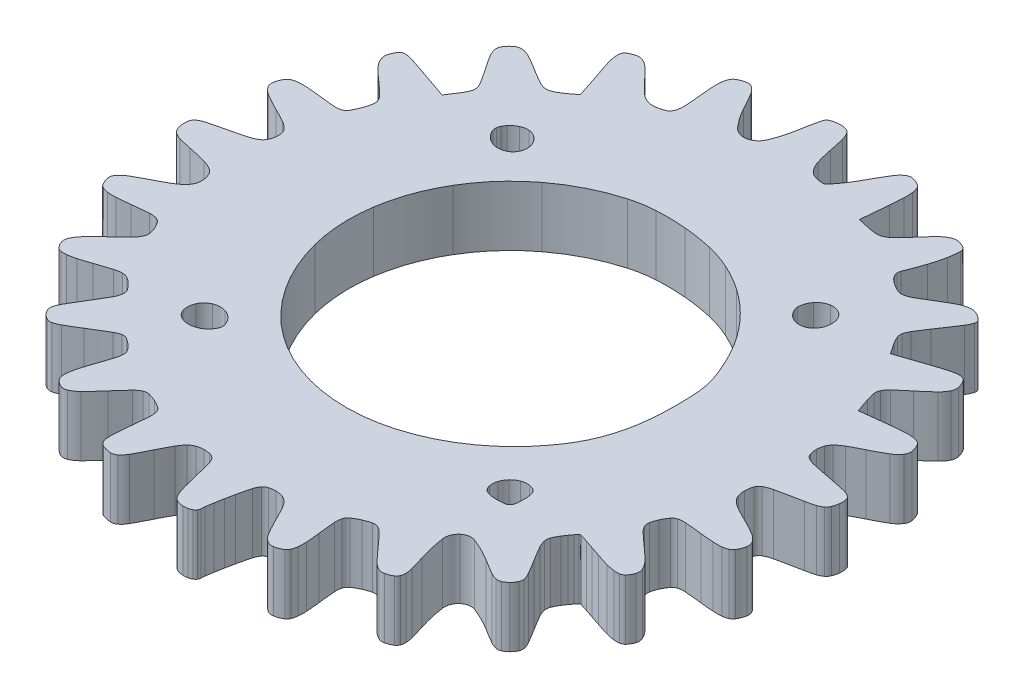
SolidWorks part; units mm, degrees
ref_plane "Front Plane" through (0, 0, 0) normal (0, 0, 1) x (1, 0, 0)
ref_plane "Top Plane" through (0, 0, 0) normal (0, 1, 0) x (1, 0, 0)
ref_plane "Right Plane" through (0, 0, 0) normal (1, 0, 0) x (0, 0, -1)
sketch "Sketch1" plane through (0, 0, 0) normal (0, 1, 0) x (1, 0, 0)
  line L117 (11035.1777, 9201.8668) -> (11035.0579, 9201.6839)
  line L118 (11035.0579, 9201.6839) -> (11034.6261, 9201.8325)
  line L119 (11043.5335, 9200.6497) -> (11043.0767, 9200.5967)
  line L120 (11043.0767, 9200.5967) -> (11042.9953, 9200.8302)
  line L121 (11042.9884, 9201.8431) -> (11042.5214, 9201.6854)
  line L122 (11042.5214, 9201.6854) -> (11042.4021, 9201.8675)
  line L123 (11040.5559, 9203.3117) -> (11040.3294, 9203.3614)
  line L124 (11040.3294, 9203.3614) -> (11040.3711, 9203.8218)
  arc A653 (11038.6129, 9204.5147) -> (11038.597, 9204.4764) centre (11038.7402, 9204.4394) ccw
  arc A654 (11038.597, 9204.4764) -> (11038.5732, 9204.3788) centre (11042.1329, 9203.5631) ccw
  arc A655 (11038.5732, 9204.3788) -> (11038.5484, 9204.261) centre (11041.9829, 9203.5975) ccw
  arc A656 (11038.5484, 9204.261) -> (11038.5253, 9204.1322) centre (11043.3345, 9203.3363) ccw
  arc A657 (11038.4093, 9203.7376) -> (11038.5253, 9204.1322) centre (11036.8563, 9204.4084) ccw
  arc A658 (11038.2209, 9203.5891) -> (11038.4093, 9203.7376) centre (11038.1778, 9203.8376) ccw
  arc A659 (11037.9966, 9203.6668) -> (11038.2209, 9203.5891) centre (11038.179, 9203.8308) ccw
  arc A660 (11037.7648, 9204.0003) -> (11037.9966, 9203.6668) centre (11039.2056, 9204.7541) ccw
  arc A661 (11037.7648, 9204.0003) -> (11037.6141, 9204.268) centre (11033.3581, 9201.6948) ccw
  arc A662 (11037.6141, 9204.268) -> (11037.5104, 9204.3797) centre (11037.2932, 9204.074) ccw
  arc A663 (11037.5104, 9204.3797) -> (11037.406, 9204.4022) centre (11037.432, 9204.2694) ccw
  arc A664 (11037.406, 9204.4022) -> (11037.2736, 9204.3494) centre (11037.4802, 9204.0231) ccw
  arc A665 (11037.2736, 9204.3494) -> (11037.2246, 9204.2922) centre (11037.3419, 9204.2415) ccw
  arc A666 (11037.2246, 9204.2922) -> (11037.1997, 9204.1986) centre (11037.526, 9204.1619) ccw
  arc A667 (11037.1997, 9204.1986) -> (11037.1958, 9204.0539) centre (11038.0452, 9204.1034) ccw
  arc A668 (11037.1958, 9204.0539) -> (11037.2145, 9203.8246) centre (11042.2008, 9204.3458) ccw
  arc A669 (11037.2351, 9203.5815) -> (11037.2145, 9203.8246) centre (11031.0398, 9203.1792) ccw
  arc A670 (11037.23, 9203.4472) -> (11037.2351, 9203.5815) centre (11036.5793, 9203.5389) ccw
  arc A671 (11037.2007, 9203.3683) -> (11037.23, 9203.4472) centre (11037.0356, 9203.4746) ccw
  arc A672 (11037.1437, 9203.322) -> (11037.2007, 9203.3683) centre (11037.1013, 9203.4323) ccw
  arc A673 (11036.9852, 9203.285) -> (11037.1437, 9203.322) centre (11036.9302, 9203.8781) ccw
  arc A674 (11036.8544, 9203.3053) -> (11036.9852, 9203.285) centre (11036.9602, 9203.5545) ccw
  arc A675 (11036.7186, 9203.3933) -> (11036.8544, 9203.3053) centre (11037.0379, 9203.7374) ccw
  arc A676 (11036.5332, 9203.5812) -> (11036.7186, 9203.3933) centre (11038.7613, 9205.5943) ccw
  arc A677 (11036.5332, 9203.5812) -> (11036.3454, 9203.7751) centre (11033.6494, 9200.9759) ccw
  arc A678 (11036.3454, 9203.7751) -> (11036.2207, 9203.859) centre (11036.045, 9203.4633) ccw
  arc A679 (11036.2207, 9203.859) -> (11036.1111, 9203.8714) centre (11036.1462, 9203.6912) ccw
  arc A680 (11036.1111, 9203.8714) -> (11035.989, 9203.8228) centre (11036.1789, 9203.5238) ccw
  arc A681 (11035.989, 9203.8228) -> (11035.9503, 9203.7692) centre (11036.037, 9203.7473) ccw
  arc A682 (11035.9503, 9203.7692) -> (11035.9444, 9203.6827) centre (11036.1848, 9203.7098) ccw
  arc A683 (11035.9444, 9203.6827) -> (11035.9725, 9203.5455) centre (11036.7209, 9203.7703) ccw
  arc A684 (11035.9725, 9203.5455) -> (11036.0462, 9203.3167) centre (11041.7937, 9205.2942) ccw
  arc A685 (11036.1049, 9203.1443) -> (11036.0462, 9203.3167) centre (11008.7323, 9193.9194) ccw
  arc A686 (11036.1543, 9202.9952) -> (11036.1049, 9203.1443) centre (11020.8775, 9198.0125) ccw
  arc A687 (11036.1965, 9202.8654) -> (11036.1543, 9202.9952) centre (10991.7342, 9188.507) ccw
  arc A688 (11036.1993, 9202.8472) -> (11036.1965, 9202.8654) centre (11036.14, 9202.8472) ccw
  arc A689 (11036.1928, 9202.8332) -> (11036.1993, 9202.8472) centre (11036.1811, 9202.8472) ccw
  arc A690 (11036.1461, 9202.7951) -> (11036.1928, 9202.8332) centre (11034.9769, 9204.2751) ccw
  arc A691 (11036.0876, 9202.7513) -> (11036.1461, 9202.7951) centre (11035.2969, 9203.8701) ccw
  arc A692 (11036.0182, 9202.7041) -> (11036.0876, 9202.7513) centre (11034.7113, 9204.6986) ccw
  arc A693 (11035.9009, 9202.6449) -> (11036.0182, 9202.7041) centre (11035.6991, 9203.191) ccw
  arc A694 (11035.8065, 9202.6382) -> (11035.9009, 9202.6449) centre (11035.8422, 9202.8038) ccw
  arc A695 (11035.6891, 9202.6833) -> (11035.8065, 9202.6382) centre (11035.8932, 9203.0398) ccw
  arc A696 (11035.4481, 9202.8271) -> (11035.6891, 9202.6833) centre (11039.5312, 9209.3954) ccw
  arc A697 (11035.4481, 9202.8271) -> (11035.2361, 9202.9524) centre (11032.5234, 9198.1222) ccw
  arc A698 (11035.2361, 9202.9524) -> (11035.111, 9203.0048) centre (11034.9474, 9202.4383) ccw
  arc A699 (11035.111, 9203.0048) -> (11035.0216, 9203.0093) centre (11035.0567, 9202.8169) ccw
  arc A700 (11035.0216, 9203.0093) -> (11034.9435, 9202.9728) centre (11035.0522, 9202.8418) ccw
  arc A701 (11034.9435, 9202.9728) -> (11034.8588, 9202.8741) centre (11035.1898, 9202.676) ccw
  arc A702 (11034.8588, 9202.8741) -> (11034.8424, 9202.7778) centre (11034.9745, 9202.8049) ccw
  arc A703 (11034.8424, 9202.7778) -> (11034.8945, 9202.6473) centre (11035.2309, 9202.8574) ccw
  arc A704 (11034.8945, 9202.6473) -> (11035.0626, 9202.391) centre (11040.7395, 9206.2969) ccw
  arc A705 (11035.2027, 9202.1782) -> (11035.0626, 9202.391) centre (11029.9216, 9198.8539) ccw
  arc A706 (11035.246, 9202.0727) -> (11035.2027, 9202.1782) centre (11034.9222, 9202.0016) ccw
  arc A707 (11035.2387, 9201.9839) -> (11035.246, 9202.0727) centre (11035.0979, 9202.0402) ccw
  arc A708 (11035.1777, 9201.8668) -> (11035.2387, 9201.9839) centre (11034.6237, 9202.2298) ccw
  arc A709 (11034.6261, 9201.8325) -> (11034.2708, 9201.9509) centre (11028.3283, 9183.5277) ccw
  arc A710 (11034.2708, 9201.9509) -> (11034.1488, 9201.9693) centre (11034.1537, 9201.5877) ccw
  arc A711 (11034.1488, 9201.9693) -> (11034.0798, 9201.9328) centre (11034.1499, 9201.8837) ccw
  arc A712 (11034.0798, 9201.9328) -> (11034.0264, 9201.8248) centre (11034.4064, 9201.7042) ccw
  arc A713 (11034.0264, 9201.8248) -> (11034.021, 9201.7326) centre (11034.2051, 9201.7681) ccw
  arc A714 (11034.021, 9201.7326) -> (11034.0587, 9201.6382) centre (11034.2861, 9201.7837) ccw
  arc A715 (11034.0587, 9201.6382) -> (11034.15, 9201.5252) centre (11034.6144, 9201.9938) ccw
  arc A716 (11034.15, 9201.5252) -> (11034.3193, 9201.3671) centre (11036.9105, 9204.3109) ccw
  arc A717 (11034.5286, 9201.1752) -> (11034.3193, 9201.3671) centre (11029.6558, 9196.0692) ccw
  arc A718 (11034.6009, 9201.0753) -> (11034.5286, 9201.1752) centre (11034.294, 9200.9293) ccw
  arc A719 (11034.6139, 9200.9785) -> (11034.6009, 9201.0753) centre (11034.4566, 9201.0066) ccw
  arc A720 (11034.5736, 9200.8322) -> (11034.6139, 9200.9785) centre (11033.8008, 9201.124) ccw
  arc A721 (11034.5074, 9200.6901) -> (11034.5736, 9200.8322) centre (11033.5986, 9201.2003) ccw
  arc A722 (11034.4405, 9200.6346) -> (11034.5074, 9200.6901) centre (11034.4015, 9200.7495) ccw
  arc A723 (11034.332, 9200.6214) -> (11034.4405, 9200.6346) centre (11034.3545, 9200.8886) ccw
  arc A724 (11034.0378, 9200.6508) -> (11034.332, 9200.6214) centre (11035.1164, 9209.9448) ccw
  arc A725 (11034.0378, 9200.6508) -> (11033.8148, 9200.6714) centre (11033.4856, 9195.8937) ccw
  arc A726 (11033.8148, 9200.6714) -> (11033.6725, 9200.6691) centre (11033.757, 9199.8321) ccw
  arc A727 (11033.6725, 9200.6691) -> (11033.5801, 9200.6459) centre (11033.7054, 9200.3429) ccw
  arc A728 (11033.5801, 9200.6459) -> (11033.5242, 9200.599) centre (11033.6262, 9200.5343) ccw
  arc A729 (11033.5242, 9200.599) -> (11033.4711, 9200.4604) centre (11033.8417, 9200.3978) ccw
  arc A730 (11033.4711, 9200.4604) -> (11033.4967, 9200.3476) centre (11033.621, 9200.4351) ccw
  arc A731 (11033.4967, 9200.3476) -> (11033.6154, 9200.238) centre (11033.8114, 9200.5692) ccw
  arc A732 (11033.6154, 9200.238) -> (11033.8786, 9200.0958) centre (11035.5589, 9203.5218) ccw
  arc A733 (11034.1113, 9199.9745) -> (11033.8786, 9200.0958) centre (11031.5049, 9195.2558) ccw
  arc A734 (11034.2221, 9199.8913) -> (11034.1113, 9199.9745) centre (11033.871, 9199.5395) ccw
  arc A735 (11034.2708, 9199.8066) -> (11034.2221, 9199.8913) centre (11034.0899, 9199.7589) ccw
  arc A736 (11034.2787, 9199.6966) -> (11034.2708, 9199.8066) centre (11033.9842, 9199.7309) ccw
  arc A737 (11034.2454, 9199.5896) -> (11034.2787, 9199.6966) centre (11033.9767, 9199.7318) ccw
  arc A738 (11034.1781, 9199.5187) -> (11034.2454, 9199.5896) centre (11034.0845, 9199.6748) ccw
  arc A739 (11034.0484, 9199.4633) -> (11034.1781, 9199.5187) centre (11033.9124, 9199.9616) ccw
  arc A740 (11033.7763, 9199.3951) -> (11034.0484, 9199.4633) centre (11032.3048, 9205.8509) ccw
  arc A741 (11033.7763, 9199.3951) -> (11033.4863, 9199.324) centre (11035.7781, 9190.6128) ccw
  arc A742 (11033.4863, 9199.324) -> (11033.3725, 9199.2729) centre (11033.5833, 9198.9554) ccw
  arc A743 (11033.3725, 9199.2729) -> (11033.325, 9199.204) centre (11033.4347, 9199.1793) ccw
  arc A744 (11033.325, 9199.204) -> (11033.3191, 9199.0916) centre (11033.6508, 9199.1305) ccw
  arc A745 (11033.3191, 9199.0916) -> (11033.3483, 9198.9861) centre (11033.674, 9199.1332) ccw
  arc A746 (11033.3483, 9198.9861) -> (11033.4057, 9198.9182) centre (11033.4963, 9199.0529) ccw
  arc A747 (11033.4057, 9198.9182) -> (11033.5126, 9198.8695) centre (11033.6054, 9199.2151) ccw
  arc A748 (11033.5126, 9198.8695) -> (11033.7228, 9198.82) centre (11034.4185, 9202.2426) ccw
  arc A749 (11034.0329, 9198.7472) -> (11033.7228, 9198.82) centre (11032.6663, 9193.6222) ccw
  arc A750 (11034.1894, 9198.6765) -> (11034.0329, 9198.7472) centre (11033.8972, 9198.2382) ccw
  arc A751 (11034.2669, 9198.5811) -> (11034.1894, 9198.6765) centre (11034.0742, 9198.5038) ccw
  arc A752 (11034.2943, 9198.439) -> (11034.2669, 9198.5811) centre (11033.9128, 9198.439) ccw
  arc A753 (11034.272, 9198.3394) -> (11034.2943, 9198.439) centre (11034.0608, 9198.439) ccw
  arc A754 (11034.2085, 9198.2523) -> (11034.272, 9198.3394) centre (11034.0122, 9198.462) ccw
  arc A755 (11034.0876, 9198.1622) -> (11034.2085, 9198.2523) centre (11033.7485, 9198.7436) ccw
  arc A756 (11033.8752, 9198.0466) -> (11034.0876, 9198.1622) centre (11032.0317, 9201.6875) ccw
  arc A757 (11033.8752, 9198.0466) -> (11033.6066, 9197.9005) centre (11036.2092, 9193.4371) ccw
  arc A758 (11033.6066, 9197.9005) -> (11033.496, 9197.8009) centre (11033.7907, 9197.5848) ccw
  arc A759 (11033.496, 9197.8009) -> (11033.4736, 9197.6998) centre (11033.5997, 9197.7249) ccw
  arc A760 (11033.4736, 9197.6998) -> (11033.5256, 9197.5698) centre (11033.8488, 9197.7744) ccw
  arc A761 (11033.5256, 9197.5698) -> (11033.5823, 9197.5214) centre (11033.6321, 9197.6372) ccw
  arc A762 (11033.5823, 9197.5214) -> (11033.6746, 9197.4972) centre (11033.7081, 9197.8141) ccw
  arc A763 (11033.6746, 9197.4972) -> (11033.8176, 9197.4945) centre (11033.7621, 9198.3244) ccw
  arc A764 (11033.8176, 9197.4945) -> (11034.0445, 9197.5149) centre (11033.4865, 9202.4473) ccw
  arc A765 (11034.3267, 9197.542) -> (11034.0445, 9197.5149) centre (11034.985, 9189.2027) ccw
  arc A766 (11034.4448, 9197.5315) -> (11034.3267, 9197.542) centre (11034.3547, 9197.1879) ccw
  arc A767 (11034.518, 9197.483) -> (11034.4448, 9197.5315) centre (11034.4102, 9197.3996) ccw
  arc A768 (11034.5842, 9197.3733) -> (11034.518, 9197.483) centre (11034.0774, 9197.1423) ccw
  arc A769 (11034.6199, 9197.2539) -> (11034.5842, 9197.3733) centre (11034.1698, 9197.1845) ccw
  arc A770 (11034.6054, 9197.1616) -> (11034.6199, 9197.2539) centre (11034.4678, 9197.2304) ccw
  arc A771 (11034.5308, 9197.058) -> (11034.6054, 9197.1616) centre (11034.2492, 9197.3396) ccw
  arc A772 (11034.3308, 9196.866) -> (11034.5308, 9197.058) centre (11029.7063, 9201.8829) ccw
  arc A773 (11034.3308, 9196.866) -> (11034.1092, 9196.6484) centre (11037.6511, 9193.2639) ccw
  arc A774 (11034.1092, 9196.6484) -> (11034.016, 9196.5092) centre (11034.4626, 9196.3107) ccw
  arc A775 (11034.016, 9196.5092) -> (11034.0088, 9196.3977) centre (11034.1633, 9196.4437) ccw
  arc A776 (11034.0088, 9196.3977) -> (11034.074, 9196.2882) centre (11034.2577, 9196.4719) ccw
  arc A777 (11034.074, 9196.2882) -> (11034.1372, 9196.2567) centre (11034.1529, 9196.3671) ccw
  arc A778 (11034.1372, 9196.2567) -> (11034.235, 9196.2557) centre (11034.19, 9196.6288) ccw
  arc A779 (11034.235, 9196.2557) -> (11034.376, 9196.2843) centre (11034.1279, 9197.1435) ccw
  arc A780 (11034.376, 9196.2843) -> (11034.5821, 9196.3495) centre (11033.1838, 9200.4136) ccw
  arc A781 (11034.8406, 9196.4338) -> (11034.5821, 9196.3495) centre (11037.3033, 9188.4399) ccw
  arc A782 (11034.963, 9196.4543) -> (11034.8406, 9196.4338) centre (11034.9791, 9195.9842) ccw
  arc A783 (11035.0508, 9196.4345) -> (11034.963, 9196.4543) centre (11034.9691, 9196.2771) ccw
  arc A784 (11035.1453, 9196.3688) -> (11035.0508, 9196.4345) centre (11034.8433, 9196.0352) ccw
  arc A785 (11035.247, 9196.253) -> (11035.1453, 9196.3688) centre (11034.6935, 9195.8696) ccw
  arc A786 (11035.2692, 9196.1563) -> (11035.247, 9196.253) centre (11035.137, 9196.1768) ccw
  arc A787 (11035.2243, 9196.0279) -> (11035.2692, 9196.1563) centre (11034.9002, 9196.2134) ccw
  arc A788 (11035.0461, 9195.7277) -> (11035.2243, 9196.0279) centre (11025.6493, 9201.5096) ccw
  arc A789 (11035.0461, 9195.7277) -> (11034.9077, 9195.494) centre (11041.8735, 9191.5268) ccw
  arc A790 (11034.9077, 9195.494) -> (11034.8637, 9195.3813) centre (11035.2695, 9195.2879) ccw
  arc A791 (11034.8637, 9195.3813) -> (11034.8717, 9195.3005) centre (11034.9876, 9195.3528) ccw
  arc A792 (11034.8717, 9195.3005) -> (11034.9287, 9195.218) centre (11035.126, 9195.4153) ccw
  arc A793 (11034.9287, 9195.218) -> (11035.0113, 9195.1611) centre (11035.1243, 9195.4136) ccw
  arc A794 (11035.0113, 9195.1611) -> (11035.0922, 9195.1534) centre (11035.0631, 9195.2769) ccw
  arc A795 (11035.0922, 9195.1534) -> (11035.205, 9195.1981) centre (11034.9961, 9195.5609) ccw
  arc A796 (11035.205, 9195.1981) -> (11035.4394, 9195.3384) centre (11031.1618, 9202.2196) ccw
  arc A797 (11035.7404, 9195.5211) -> (11035.4394, 9195.3384) centre (11044.2561, 9181.1551) ccw
  arc A798 (11035.8508, 9195.5633) -> (11035.7404, 9195.5211) centre (11035.9185, 9195.2206) ccw
  arc A799 (11035.9365, 9195.5479) -> (11035.8508, 9195.5633) centre (11035.8739, 9195.4464) ccw
  arc A800 (11036.0538, 9195.4598) -> (11035.9365, 9195.5479) centre (11035.515, 9194.8644) ccw
  arc A801 (11036.1246, 9195.3758) -> (11036.0538, 9195.4598) centre (11035.7791, 9195.1563) ccw
  arc A802 (11036.1468, 9195.2957) -> (11036.1246, 9195.3758) centre (11036.0039, 9195.2991) ccw
  arc A803 (11036.1277, 9195.1797) -> (11036.1468, 9195.2957) centre (11035.7243, 9195.3057) ccw
  arc A804 (11036.0409, 9194.9149) -> (11036.1277, 9195.1797) centre (11026.8462, 9198.0784) ccw
  arc A805 (11036.0409, 9194.9149) -> (11035.9741, 9194.7036) centre (11040.2145, 9193.479) ccw
  arc A806 (11035.9741, 9194.7036) -> (11035.9454, 9194.5608) centre (11036.8147, 9194.4608) ccw
  arc A807 (11035.9454, 9194.5608) -> (11035.9476, 9194.46) centre (11036.3162, 9194.5182) ccw
  arc A808 (11035.9476, 9194.46) -> (11035.9802, 9194.3877) centre (11036.0954, 9194.4833) ccw
  arc A809 (11035.9802, 9194.3877) -> (11036.0857, 9194.309) centre (11036.196, 9194.5667) ccw
  arc A810 (11036.0857, 9194.309) -> (11036.1929, 9194.3095) centre (11036.1388, 9194.4331) ccw
  arc A811 (11036.1929, 9194.3095) -> (11036.3273, 9194.4018) centre (11036.0193, 9194.706) ccw
  arc A812 (11036.3273, 9194.4018) -> (11036.5426, 9194.634) centre (11032.7198, 9197.9641) ccw
  arc A813 (11036.7387, 9194.851) -> (11036.5426, 9194.634) centre (11042.6359, 9189.3262) ccw
  arc A814 (11036.8358, 9194.9222) -> (11036.7387, 9194.851) centre (11036.9772, 9194.6276) ccw
  arc A815 (11036.9279, 9194.9322) -> (11036.8358, 9194.9222) centre (11036.896, 9194.7967) ccw
  arc A816 (11037.0659, 9194.885) -> (11036.9279, 9194.9322) centre (11036.7574, 9194.208) ccw
  arc A817 (11037.1951, 9194.8114) -> (11037.0659, 9194.885) centre (11036.7237, 9194.1342) ccw
  arc A818 (11037.2489, 9194.737) -> (11037.1951, 9194.8114) centre (11037.1156, 9194.6973) ccw
  arc A819 (11037.2619, 9194.6186) -> (11037.2489, 9194.737) centre (11036.9304, 9194.6421) ccw
  arc A820 (11037.2357, 9194.3153) -> (11037.2619, 9194.6186) centre (11027.5857, 9195.304) ccw
  arc A821 (11037.2357, 9194.3153) -> (11037.2144, 9194.0614) centre (11044.0786, 9193.6142) ccw
  arc A822 (11037.2144, 9194.0614) -> (11037.2196, 9193.925) centre (11037.8755, 9194.0183) ccw
  arc A823 (11037.2196, 9193.925) -> (11037.25, 9193.8455) centre (11037.4093, 9193.952) ccw
  arc A824 (11037.25, 9193.8455) -> (11037.3092, 9193.7982) centre (11037.3541, 9193.9151) ccw
  arc A825 (11037.3092, 9193.7982) -> (11037.4516, 9193.765) centre (11037.4998, 9194.2949) ccw
  arc A826 (11037.4516, 9193.765) -> (11037.5481, 9193.7939) centre (11037.4639, 9193.8999) ccw
  arc A827 (11037.5481, 9193.7939) -> (11037.6368, 9193.8989) centre (11037.331, 9194.0673) ccw
  arc A828 (11037.6368, 9193.8989) -> (11037.7781, 9194.1705) centre (11031.9657, 9197.0212) ccw
  arc A829 (11037.8967, 9194.3965) -> (11037.7781, 9194.1705) centre (11041.9659, 9192.1167) ccw
  arc A830 (11037.9835, 9194.5124) -> (11037.8967, 9194.3965) centre (11038.377, 9194.1274) ccw
  arc A831 (11038.0729, 9194.5697) -> (11037.9835, 9194.5124) centre (11038.1524, 9194.3471) ccw
  arc A832 (11038.1881, 9194.5896) -> (11038.0729, 9194.5697) centre (11038.1881, 9194.2471) ccw
  arc A833 (11038.2919, 9194.5792) -> (11038.1881, 9194.5896) centre (11038.1881, 9194.07) ccw
  arc A834 (11038.3608, 9194.5464) -> (11038.2919, 9194.5792) centre (11038.2603, 9194.424) ccw
  arc A835 (11038.408, 9194.4841) -> (11038.3608, 9194.5464) centre (11038.2539, 9194.4162) ccw
  arc A836 (11038.4432, 9194.3801) -> (11038.408, 9194.4841) centre (11037.8431, 9194.2352) ccw
  arc A837 (11038.4432, 9194.3801) -> (11038.5666, 9193.8866) centre (11068.7521, 9201.6963) ccw
  arc A838 (11038.5666, 9193.8866) -> (11038.6332, 9193.7079) centre (11039.4563, 9194.1168) ccw
  arc A839 (11038.6332, 9193.7079) -> (11038.7114, 9193.6283) centre (11038.7944, 9193.788) ccw
  arc A840 (11038.7114, 9193.6283) -> (11038.8312, 9193.599) centre (11038.8312, 9193.8587) ccw
  arc A841 (11038.8312, 9193.599) -> (11038.9077, 9193.6066) centre (11038.8312, 9193.992) ccw
  arc A842 (11038.9077, 9193.6066) -> (11038.9674, 9193.6293) centre (11038.8706, 9193.7936) ccw
  arc A843 (11038.9674, 9193.6293) -> (11039.0051, 9193.6648) centre (11038.9079, 9193.7303) ccw
  arc A844 (11039.0051, 9193.6648) -> (11039.0187, 9193.7096) centre (11038.9386, 9193.7096) ccw
  arc A845 (11039.0234, 9193.7742) -> (11039.0187, 9193.7096) centre (11039.4732, 9193.7096) ccw
  arc A846 (11039.043, 9193.9007) -> (11039.0234, 9193.7742) centre (11044.6941, 9192.9593) ccw
  arc A847 (11039.0697, 9194.0495) -> (11039.043, 9193.9007) centre (11045.0684, 9192.8969) ccw
  arc A848 (11039.1012, 9194.2049) -> (11039.0697, 9194.0495) centre (11046.3352, 9192.6535) ccw
  arc A849 (11039.1554, 9194.4283) -> (11039.1012, 9194.2049) centre (11043.3501, 9193.2937) ccw
  arc A850 (11039.2038, 9194.5275) -> (11039.1554, 9194.4283) centre (11039.4374, 9194.3521) ccw
  arc A851 (11039.2733, 9194.5744) -> (11039.2038, 9194.5275) centre (11039.3063, 9194.4505) ccw
  arc A852 (11039.3902, 9194.5896) -> (11039.2733, 9194.5744) centre (11039.3902, 9194.1351) ccw
  arc A853 (11039.5067, 9194.5699) -> (11039.3902, 9194.5896) centre (11039.3902, 9194.2367) ccw
  arc A854 (11039.5964, 9194.5129) -> (11039.5067, 9194.5699) centre (11039.4294, 9194.3487) ccw
  arc A855 (11039.6831, 9194.3974) -> (11039.5964, 9194.5129) centre (11039.2086, 9194.1317) ccw
  arc A856 (11039.8021, 9194.1705) -> (11039.6831, 9194.3974) centre (11035.5761, 9192.0979) ccw
  arc A857 (11039.8021, 9194.1705) -> (11039.9433, 9193.9094) centre (11043.1629, 9195.8188) ccw
  arc A858 (11039.9433, 9193.9094) -> (11040.0526, 9193.7916) centre (11040.2711, 9194.1038) ccw
  arc A859 (11040.0526, 9193.7916) -> (11040.1652, 9193.7663) centre (11040.1396, 9193.916) ccw
  arc A860 (11040.1652, 9193.7663) -> (11040.3036, 9193.8196) centre (11040.1016, 9194.1384) ccw
  arc A861 (11040.3036, 9193.8196) -> (11040.3507, 9193.8756) centre (11040.2391, 9193.9215) ccw
  arc A862 (11040.3507, 9193.8756) -> (11040.3738, 9193.9684) centre (11040.0457, 9194.001) ccw
  arc A863 (11040.3738, 9193.9684) -> (11040.3759, 9194.1117) centre (11039.5265, 9194.0526) ccw
  arc A864 (11040.3759, 9194.1117) -> (11040.355, 9194.3369) centre (11035.4778, 9193.7709) ccw
  arc A865 (11040.3263, 9194.6268) -> (11040.355, 9194.3369) centre (11049.052, 9195.3463) ccw
  arc A866 (11040.3381, 9194.7417) -> (11040.3263, 9194.6268) centre (11040.6392, 9194.6526) ccw
  arc A867 (11040.3908, 9194.8145) -> (11040.3381, 9194.7417) centre (11040.4681, 9194.7032) ccw
  arc A868 (11040.5179, 9194.887) -> (11040.3908, 9194.8145) centre (11040.86, 9194.1392) ccw
  arc A869 (11040.6539, 9194.9332) -> (11040.5179, 9194.887) centre (11040.8114, 9194.2454) ccw
  arc A870 (11040.7463, 9194.9228) -> (11040.6539, 9194.9332) centre (11040.6853, 9194.7959) ccw
  arc A871 (11040.8446, 9194.8512) -> (11040.7463, 9194.9228) centre (11040.6008, 9194.6199) ccw
  arc A872 (11041.0422, 9194.6352) -> (11040.8446, 9194.8512) centre (11034.9927, 9189.3007) ccw
  arc A873 (11041.0422, 9194.6352) -> (11041.2542, 9194.4054) centre (11046.2114, 9199.1935) ccw
  arc A874 (11041.2542, 9194.4054) -> (11041.3742, 9194.3167) centre (11041.5796, 9194.7197) ccw
  arc A875 (11041.3742, 9194.3167) -> (11041.4768, 9194.303) centre (11041.4448, 9194.4553) ccw
  arc A876 (11041.4768, 9194.303) -> (11041.5976, 9194.352) centre (11041.4017, 9194.6611) ccw
  arc A877 (11041.5976, 9194.352) -> (11041.6426, 9194.4061) centre (11041.5363, 9194.4488) ccw
  arc A878 (11041.6426, 9194.4061) -> (11041.6552, 9194.4847) centre (11041.475, 9194.4734) ccw
  arc A879 (11041.6552, 9194.4847) -> (11041.6342, 9194.6106) centre (11041.034, 9194.4458) ccw
  arc A880 (11041.6342, 9194.6106) -> (11041.5672, 9194.8379) centre (11035.5292, 9192.9346) ccw
  arc A881 (11041.4639, 9195.2861) -> (11041.5672, 9194.8379) centre (11044.3503, 9195.7152) ccw
  arc A882 (11041.5407, 9195.4975) -> (11041.4639, 9195.2861) centre (11041.6976, 9195.3209) ccw
  arc A883 (11041.7499, 9195.5349) -> (11041.5407, 9195.4975) centre (11041.6759, 9195.3454) ccw
  arc A884 (11042.1347, 9195.3422) -> (11041.7499, 9195.5349) centre (11040.8968, 9193.3508) ccw
  arc A885 (11042.1347, 9195.3422) -> (11042.3756, 9195.1978) centre (11046.7446, 9202.7579) ccw
  arc A886 (11042.3756, 9195.1978) -> (11042.4886, 9195.1531) centre (11042.5825, 9195.5559) ccw
  arc A887 (11042.4886, 9195.1531) -> (11042.5699, 9195.1616) centre (11042.517, 9195.2747) ccw
  arc A888 (11042.5699, 9195.1616) -> (11042.6546, 9195.221) centre (11042.4431, 9195.4325) ccw
  arc A889 (11042.6546, 9195.221) -> (11042.714, 9195.3056) centre (11042.4419, 9195.4336) ccw
  arc A890 (11042.714, 9195.3056) -> (11042.7226, 9195.3867) centre (11042.6014, 9195.3586) ccw
  arc A891 (11042.7226, 9195.3867) -> (11042.6782, 9195.4993) centre (11042.3231, 9195.2941) ccw
  arc A892 (11042.6782, 9195.4993) -> (11042.5346, 9195.7389) centre (11035.1954, 9191.1766) ccw
  arc A893 (11042.3889, 9195.9828) -> (11042.5346, 9195.7389) centre (11049.2866, 9199.9362) ccw
  arc A894 (11042.3433, 9196.1012) -> (11042.3889, 9195.9828) centre (11042.7514, 9196.1906) ccw
  arc A895 (11042.3497, 9196.1961) -> (11042.3433, 9196.1012) centre (11042.5094, 9196.1376) ccw
  arc A896 (11042.4087, 9196.3135) -> (11042.3497, 9196.1961) centre (11042.8904, 9195.9979) ccw
  arc A897 (11042.456, 9196.3829) -> (11042.4087, 9196.3135) centre (11044.4033, 9195.0066) ccw
  arc A898 (11042.4997, 9196.4414) -> (11042.456, 9196.3829) centre (11043.5748, 9195.5922) ccw
  arc A899 (11042.5379, 9196.4882) -> (11042.4997, 9196.4414) centre (11043.9798, 9195.2722) ccw
  arc A900 (11042.5519, 9196.4946) -> (11042.5379, 9196.4882) centre (11042.5519, 9196.4764) ccw
  arc A901 (11042.57, 9196.4918) -> (11042.5519, 9196.4946) centre (11042.5519, 9196.4354) ccw
  arc A902 (11042.6933, 9196.4519) -> (11042.57, 9196.4918) centre (11030.2017, 9158.0477) ccw
  arc A903 (11042.8352, 9196.4049) -> (11042.6933, 9196.4519) centre (11038.184, 9182.5886) ccw
  arc A904 (11042.999, 9196.3492) -> (11042.8352, 9196.4049) centre (11034.5167, 9171.6948) ccw
  arc A905 (11042.999, 9196.3492) -> (11043.2047, 9196.2842) centre (11044.3919, 9200.3976) ccw
  arc A906 (11043.2047, 9196.2842) -> (11043.3455, 9196.2556) centre (11043.4518, 9197.1405) ccw
  arc A907 (11043.3455, 9196.2556) -> (11043.4431, 9196.2567) centre (11043.3902, 9196.6276) ccw
  arc A908 (11043.4431, 9196.2567) -> (11043.5062, 9196.2882) centre (11043.4273, 9196.3671) ccw
  arc A909 (11043.5062, 9196.2882) -> (11043.5721, 9196.3994) centre (11043.3221, 9196.4724) ccw
  arc A910 (11043.5721, 9196.3994) -> (11043.564, 9196.5126) centre (11043.4154, 9196.4451) ccw
  arc A911 (11043.564, 9196.5126) -> (11043.4683, 9196.6516) centre (11043.1272, 9196.3142) ccw
  arc A912 (11043.4683, 9196.6516) -> (11043.2459, 9196.8614) centre (11040.3186, 9193.5358) ccw
  arc A913 (11043.0397, 9197.0503) -> (11043.2459, 9196.8614) centre (11047.9403, 9202.1945) ccw
  arc A914 (11042.9661, 9197.1496) -> (11043.0397, 9197.0503) centre (11043.2888, 9197.3118) ccw
  arc A915 (11042.9531, 9197.2407) -> (11042.9661, 9197.1496) centre (11043.0949, 9197.2144) ccw
  arc A916 (11042.9925, 9197.3655) -> (11042.9531, 9197.2407) centre (11043.4816, 9197.1426) ccw
  arc A917 (11043.0607, 9197.4811) -> (11042.9925, 9197.3655) centre (11043.5732, 9197.1009) ccw
  arc A918 (11043.1338, 9197.5312) -> (11043.0607, 9197.4811) centre (11043.1698, 9197.4002) ccw
  arc A919 (11043.2508, 9197.5423) -> (11043.1338, 9197.5312) centre (11043.224, 9197.2034) ccw
  arc A920 (11043.5357, 9197.5149) -> (11043.2508, 9197.5423) centre (11042.5801, 9189.0681) ccw
  arc A921 (11043.5357, 9197.5149) -> (11043.7627, 9197.4945) centre (11044.0938, 9202.4473) ccw
  arc A922 (11043.7627, 9197.4945) -> (11043.9056, 9197.4972) centre (11043.8182, 9198.3244) ccw
  arc A923 (11043.9056, 9197.4972) -> (11043.9979, 9197.5214) centre (11043.8721, 9197.8141) ccw
  arc A924 (11043.9979, 9197.5214) -> (11044.0547, 9197.5698) centre (11043.9481, 9197.6372) ccw
  arc A925 (11044.0547, 9197.5698) -> (11044.109, 9197.7095) centre (11043.7262, 9197.7778) ccw
  arc A926 (11044.109, 9197.7095) -> (11044.0843, 9197.8226) centre (11043.9597, 9197.7361) ccw
  arc A927 (11044.0843, 9197.8226) -> (11043.9668, 9197.9319) centre (11043.7745, 9197.6076) ccw
  arc A928 (11043.9668, 9197.9319) -> (11043.705, 9198.0734) centre (11042.0517, 9194.7024) ccw
  arc A929 (11043.476, 9198.1935) -> (11043.705, 9198.0734) centre (11045.8232, 9202.3924) ccw
  arc A930 (11043.3613, 9198.28) -> (11043.476, 9198.1935) centre (11043.7336, 9198.6544) ccw
  arc A931 (11043.3053, 9198.3705) -> (11043.3613, 9198.28) centre (11043.5232, 9198.4429) ccw
  arc A932 (11043.2859, 9198.4903) -> (11043.3053, 9198.3705) centre (11043.666, 9198.4903) ccw
  arc A933 (11043.3066, 9198.6264) -> (11043.2859, 9198.4903) centre (11043.7438, 9198.4903) ccw
  arc A934 (11043.3685, 9198.7017) -> (11043.3066, 9198.6264) centre (11043.4302, 9198.5879) ccw
  arc A935 (11043.509, 9198.7536) -> (11043.3685, 9198.7017) centre (11043.6205, 9198.2365) ccw
  arc A936 (11043.9336, 9198.8411) -> (11043.509, 9198.7536) centre (11048.4057, 9176.0538) ccw
  arc A937 (11043.9336, 9198.8411) -> (11044.0952, 9198.8808) centre (11043.5906, 9200.589) ccw
  arc A938 (11044.0952, 9198.8808) -> (11044.185, 9198.927) centre (11044.019, 9199.1389) ccw
  arc A939 (11044.185, 9198.927) -> (11044.2353, 9198.9942) centre (11044.0856, 9199.0539) ccw
  arc A940 (11044.2353, 9198.9942) -> (11044.2616, 9199.0981) centre (11043.8547, 9199.146) ccw
  arc A941 (11044.2616, 9199.0981) -> (11044.2563, 9199.2132) centre (11043.9093, 9199.1395) ccw
  arc A942 (11044.2563, 9199.2132) -> (11044.2089, 9199.2803) centre (11044.1546, 9199.1916) ccw
  arc A943 (11044.2089, 9199.2803) -> (11044.0939, 9199.3266) centre (11044.0138, 9198.9614) ccw
  arc A944 (11044.0939, 9199.3266) -> (11043.7854, 9199.3895) centre (11041.7989, 9188.8617) ccw
  arc A945 (11043.4813, 9199.452) -> (11043.7854, 9199.3895) centre (11045.5592, 9208.7901) ccw
  arc A946 (11043.3604, 9199.5001) -> (11043.4813, 9199.452) centre (11043.5702, 9199.8513) ccw
  arc A947 (11043.3048, 9199.5696) -> (11043.3604, 9199.5001) centre (11043.4256, 9199.6092) ccw
  arc A948 (11043.2859, 9199.6878) -> (11043.3048, 9199.5696) centre (11043.6655, 9199.6878) ccw
  arc A949 (11043.3059, 9199.8028) -> (11043.2859, 9199.6878) centre (11043.6266, 9199.6878) ccw
  arc A950 (11043.3633, 9199.8922) -> (11043.3059, 9199.8028) centre (11043.5287, 9199.7229) ccw
  arc A951 (11043.4793, 9199.9789) -> (11043.3633, 9199.8922) centre (11043.749, 9199.4976) ccw
  arc A952 (11043.705, 9200.0974) -> (11043.4793, 9199.9789) centre (11045.7554, 9195.9167) ccw
  arc A953 (11043.705, 9200.0974) -> (11043.9662, 9200.2386) centre (11042.0567, 9203.4582) ccw
  arc A954 (11043.9662, 9200.2386) -> (11044.084, 9200.3479) centre (11043.7718, 9200.5664) ccw
  arc A955 (11044.084, 9200.3479) -> (11044.1092, 9200.4605) centre (11043.9596, 9200.4349) ccw
  arc A956 (11044.1092, 9200.4605) -> (11044.056, 9200.599) centre (11043.7372, 9200.3969) ccw
  arc A957 (11044.056, 9200.599) -> (11043.9997, 9200.6461) centre (11043.9542, 9200.5344) ccw
  arc A958 (11043.9997, 9200.6461) -> (11043.9064, 9200.6691) centre (11043.8742, 9200.3384) ccw
  arc A959 (11043.9064, 9200.6691) -> (11043.7618, 9200.671) centre (11043.8226, 9199.8078) ccw
  arc A960 (11043.7618, 9200.671) -> (11043.5335, 9200.6497) centre (11044.1186, 9195.6083) ccw
  arc A961 (11042.9593, 9200.9751) -> (11042.9953, 9200.8302) centre (11043.7643, 9201.0983) ccw
  arc A962 (11042.9743, 9201.0701) -> (11042.9593, 9200.9751) centre (11043.1155, 9200.999) ccw
  arc A963 (11043.0474, 9201.1655) -> (11042.9743, 9201.0701) centre (11043.2629, 9200.9249) ccw
  arc A964 (11043.2523, 9201.3411) -> (11043.0474, 9201.1655) centre (11047.1561, 9196.577) ccw
  arc A965 (11043.2523, 9201.3411) -> (11043.4693, 9201.5312) centre (11040.4613, 9204.7471) ccw
  arc A966 (11043.4693, 9201.5312) -> (11043.5606, 9201.6549) centre (11043.1811, 9201.8393) ccw
  arc A967 (11043.5606, 9201.6549) -> (11043.5744, 9201.7662) centre (11043.4046, 9201.7307) ccw
  arc A968 (11043.5744, 9201.7662) -> (11043.5218, 9201.8957) centre (11043.1905, 9201.6858) ccw
  arc A969 (11043.5218, 9201.8957) -> (11043.4647, 9201.9412) centre (11043.4273, 9201.8358) ccw
  arc A970 (11043.4647, 9201.9412) -> (11043.3802, 9201.9515) centre (11043.3994, 9201.7569) ccw
  arc A971 (11043.3802, 9201.9515) -> (11043.2427, 9201.9243) centre (11043.4511, 9201.232) ccw
  arc A972 (11043.2427, 9201.9243) -> (11042.9884, 9201.8431) centre (11045.5606, 9194.2261) ccw
  arc A973 (11042.3411, 9201.9835) -> (11042.4021, 9201.8675) centre (11042.973, 9202.2416) ccw
  arc A974 (11042.3328, 9202.071) -> (11042.3411, 9201.9835) centre (11042.4819, 9202.041) ccw
  arc A975 (11042.3734, 9202.174) -> (11042.3328, 9202.071) centre (11042.6418, 9202.0088) ccw
  arc A976 (11042.5047, 9202.3773) -> (11042.3734, 9202.174) centre (11047.0808, 9199.278) ccw
  arc A977 (11042.5047, 9202.3773) -> (11042.7282, 9202.7132) centre (11021.892, 9216.3376) ccw
  arc A978 (11042.7282, 9202.7132) -> (11042.7812, 9202.8289) centre (11042.3722, 9202.946) ccw
  arc A979 (11042.7812, 9202.8289) -> (11042.7643, 9202.9023) centre (11042.7063, 9202.8503) ccw
  arc A980 (11042.7643, 9202.9023) -> (11042.6751, 9202.9723) centre (11042.5209, 9202.6842) ccw
  arc A981 (11042.6751, 9202.9723) -> (11042.5761, 9203.0038) centre (11042.5405, 9202.7208) ccw
  arc A982 (11042.5761, 9203.0038) -> (11042.4752, 9202.9965) centre (11042.544, 9202.7484) ccw
  arc A983 (11042.4752, 9202.9965) -> (11042.3452, 9202.9437) centre (11042.6386, 9202.4071) ccw
  arc A984 (11042.3452, 9202.9437) -> (11042.1376, 9202.8232) centre (11044.5923, 9198.834) ccw
  arc A985 (11041.8974, 9202.6813) -> (11042.1376, 9202.8232) centre (11038.0568, 9209.4555) ccw
  arc A986 (11041.7842, 9202.6398) -> (11041.8974, 9202.6813) centre (11041.7164, 9203.0004) ccw
  arc A987 (11041.6906, 9202.6496) -> (11041.7842, 9202.6398) centre (11041.7538, 9202.8017) ccw
  arc A988 (11041.5657, 9202.7157) -> (11041.6906, 9202.6496) centre (11041.9818, 9203.3509) ccw
  arc A989 (11041.4845, 9202.7784) -> (11041.5657, 9202.7157) centre (11041.9314, 9203.2739) ccw
  arc A990 (11041.434, 9202.8408) -> (11041.4845, 9202.7784) centre (11041.6568, 9202.9695) ccw
  arc A991 (11041.4138, 9202.9027) -> (11041.434, 9202.8408) centre (11041.5694, 9202.919) ccw
  arc A992 (11041.4224, 9202.9639) -> (11041.4138, 9202.9027) centre (11041.5412, 9202.9161) ccw
  arc A993 (11041.4224, 9202.9639) -> (11041.5408, 9203.2874) centre (11036.3948, 9204.9873) ccw
  arc A994 (11041.5408, 9203.2874) -> (11041.609, 9203.5494) centre (11039.5492, 9203.9453) ccw
  arc A995 (11041.609, 9203.5494) -> (11041.6309, 9203.7432) centre (11040.3688, 9203.7878) ccw
  arc A996 (11041.6309, 9203.7432) -> (11041.5879, 9203.8248) centre (11041.5381, 9203.7465) ccw
  arc A997 (11041.5879, 9203.8248) -> (11041.4658, 9203.8723) centre (11041.4068, 9203.5399) ccw
  arc A998 (11041.4658, 9203.8723) -> (11041.3552, 9203.8578) centre (11041.4334, 9203.6898) ccw
  arc A999 (11041.3552, 9203.8578) -> (11041.2306, 9203.7704) centre (11041.5384, 9203.4646) ccw
  arc A1000 (11041.2306, 9203.7704) -> (11041.0495, 9203.574) centre (11043.7829, 9201.2343) ccw
  arc A1001 (11040.8925, 9203.4016) -> (11041.0495, 9203.574) centre (11038.1614, 9206.0461) ccw
  arc A1002 (11040.7893, 9203.324) -> (11040.8925, 9203.4016) centre (11040.595, 9203.6897) ccw
  arc A1003 (11040.6888, 9203.2982) -> (11040.7893, 9203.324) centre (11040.6858, 9203.5189) ccw
  arc A1004 (11040.5559, 9203.3117) -> (11040.6888, 9203.2982) centre (11040.6807, 9203.88) ccw
  arc A1005 (11040.3711, 9203.8218) -> (11040.3864, 9204.0498) centre (11035.5448, 9204.2594) ccw
  arc A1006 (11040.3864, 9204.0498) -> (11040.3806, 9204.1967) centre (11039.4973, 9204.0883) ccw
  arc A1007 (11040.3806, 9204.1967) -> (11040.355, 9204.2924) centre (11040.027, 9204.1533) ccw
  arc A1008 (11040.355, 9204.2924) -> (11040.3064, 9204.3497) centre (11040.2389, 9204.2432) ccw
  arc A1009 (11040.3064, 9204.3497) -> (11040.1763, 9204.4016) centre (11040.102, 9204.027) ccw
  arc A1010 (11040.1763, 9204.4016) -> (11040.0742, 9204.3797) centre (11040.1507, 9204.2723) ccw
  arc A1011 (11040.0742, 9204.3797) -> (11039.9714, 9204.2698) centre (11040.2937, 9204.0715) ccw
  arc A1012 (11039.9714, 9204.2698) -> (11039.8162, 9204.0006) centre (11044.6128, 9201.4132) ccw
  arc A1013 (11039.7231, 9203.8401) -> (11039.8162, 9204.0006) centre (11037.1546, 9205.4363) ccw
  arc A1014 (11039.6305, 9203.7047) -> (11039.7231, 9203.8401) centre (11038.1463, 9204.82) ccw
  arc A1015 (11039.5474, 9203.6025) -> (11039.6305, 9203.7047) centre (11038.238, 9204.7511) ccw
  arc A1016 (11039.5012, 9203.5815) -> (11039.5474, 9203.6025) centre (11039.501, 9203.6432) ccw
  arc A1017 (11039.3453, 9203.61) -> (11039.5012, 9203.5815) centre (11039.4999, 9204.0151) ccw
  arc A1018 (11039.2352, 9203.6921) -> (11039.3453, 9203.61) centre (11039.435, 9203.8451) ccw
  arc A1019 (11039.1551, 9203.849) -> (11039.2352, 9203.6921) centre (11039.6237, 9203.9896) ccw
  arc A1020 (11039.0874, 9204.1219) -> (11039.1551, 9203.849) centre (11041.9242, 9204.68) ccw
  arc A1021 (11039.0874, 9204.1219) -> (11039.0317, 9204.3763) centre (11033.1215, 9202.9482) ccw
  arc A1022 (11039.0317, 9204.3763) -> (11038.9839, 9204.4945) centre (11038.6091, 9204.2741) ccw
  arc A1023 (11038.9839, 9204.4945) -> (11038.9199, 9204.5514) centre (11038.8638, 9204.4239) ccw
  arc A1024 (11038.9199, 9204.5514) -> (11038.8228, 9204.5718) centre (11038.8228, 9204.3308) ccw
  arc A1025 (11038.8228, 9204.5718) -> (11038.7529, 9204.5676) centre (11038.8228, 9203.9886) ccw
  arc A1026 (11038.7529, 9204.5676) -> (11038.6885, 9204.5551) centre (11038.8069, 9204.1201) ccw
  arc A1027 (11038.6885, 9204.5551) -> (11038.6376, 9204.5368) centre (11038.7787, 9204.224) ccw
  arc A1028 (11038.6376, 9204.5368) -> (11038.6129, 9204.5147) centre (11038.6601, 9204.4868) ccw
  arc A1029 (11036.5265, 9201.55) -> (11036.5067, 9201.7476) centre (11036.2776, 9201.625) ccw
  arc A1030 (11036.3999, 9201.4076) -> (11036.5265, 9201.55) centre (11036.3096, 9201.6153) ccw
  arc A1031 (11036.1911, 9201.4003) -> (11036.3999, 9201.4076) centre (11036.2862, 9201.6694) ccw
  arc A1032 (11036.021, 9201.5365) -> (11036.1911, 9201.4003) centre (11036.3013, 9201.7121) ccw
  arc A1033 (11035.9899, 9201.6023) -> (11036.021, 9201.5365) centre (11036.2841, 9201.7014) ccw
  arc A1034 (11035.9826, 9201.662) -> (11035.9899, 9201.6023) centre (11036.1307, 9201.6497) ccw
  arc A1035 (11035.9996, 9201.7209) -> (11035.9826, 9201.662) centre (11036.1376, 9201.6491) ccw
  arc A1036 (11036.0416, 9201.7842) -> (11035.9996, 9201.7209) centre (11036.3163, 9201.5562) ccw
  arc A1037 (11036.1564, 9201.8741) -> (11036.0416, 9201.7842) centre (11036.3067, 9201.5642) ccw
  arc A1038 (11036.289, 9201.8991) -> (11036.1564, 9201.8741) centre (11036.2688, 9201.6423) ccw
  arc A1039 (11036.4137, 9201.8536) -> (11036.289, 9201.8991) centre (11036.2696, 9201.6525) ccw
  arc A1040 (11036.5067, 9201.7476) -> (11036.4137, 9201.8536) centre (11036.2326, 9201.6009) ccw
  arc A1041 (11041.5824, 9201.5212) -> (11041.5977, 9201.6805) centre (11041.2591, 9201.6327) ccw
  arc A1042 (11041.4958, 9201.3984) -> (11041.5824, 9201.5212) centre (11041.3273, 9201.6092) ccw
  arc A1043 (11041.3621, 9201.3463) -> (11041.4958, 9201.3984) centre (11041.3452, 9201.5868) ccw
  arc A1044 (11041.218, 9201.3771) -> (11041.3621, 9201.3463) centre (11041.3435, 9201.6116) ccw
  arc A1045 (11041.1637, 9201.4161) -> (11041.218, 9201.3771) centre (11041.3376, 9201.6005) ccw
  arc A1046 (11041.1178, 9201.4702) -> (11041.1637, 9201.4161) centre (11041.3838, 9201.6496) ccw
  arc A1047 (11041.0866, 9201.5304) -> (11041.1178, 9201.4702) centre (11041.3625, 9201.6352) ccw
  arc A1048 (11041.0761, 9201.5875) -> (11041.0866, 9201.5304) centre (11041.2369, 9201.5875) ccw
  arc A1049 (11041.1449, 9201.784) -> (11041.0761, 9201.5875) centre (11041.3913, 9201.5875) ccw
  arc A1050 (11041.3192, 9201.8878) -> (11041.1449, 9201.784) centre (11041.3697, 9201.6047) ccw
  arc A1051 (11041.501, 9201.8444) -> (11041.3192, 9201.8878) centre (11041.3603, 9201.6574) ccw
  arc A1052 (11041.5977, 9201.6805) -> (11041.501, 9201.8444) centre (11041.3516, 9201.6458) ccw
  arc A1053 (11040.31, 9201.3351) -> (11039.8924, 9201.5729) centre (11038.7597, 9199.0987) ccw
  arc A1054 (11040.6819, 9201.0263) -> (11040.31, 9201.3351) centre (11038.7221, 9199.0445) ccw
  arc A1055 (11040.9965, 9200.6562) -> (11040.6819, 9201.0263) centre (11038.703, 9199.0252) ccw
  arc A1056 (11041.2438, 9200.2366) -> (11040.9965, 9200.6562) centre (11038.677, 9199.0067) ccw
  arc A1057 (11041.3738, 9199.9403) -> (11041.2438, 9200.2366) centre (11036.8801, 9198.1457) ccw
  arc A1058 (11041.4427, 9199.7146) -> (11041.3738, 9199.9403) centre (11040.0607, 9199.4159) ccw
  arc A1059 (11041.475, 9199.4737) -> (11041.4427, 9199.7146) centre (11039.9443, 9199.3908) ccw
  arc A1060 (11041.4843, 9199.1235) -> (11041.475, 9199.4737) centre (11035.1468, 9199.1308) ccw
  arc A1061 (11041.4412, 9198.5541) -> (11041.4843, 9199.1235) centre (11037.648, 9199.128) ccw
  arc A1062 (11041.3123, 9198.0719) -> (11041.4412, 9198.5541) centre (11039.2119, 9198.8914) ccw
  arc A1063 (11041.0848, 9197.6419) -> (11041.3123, 9198.0719) centre (11039.3336, 9198.8439) ccw
  arc A1064 (11040.7455, 9197.2298) -> (11041.0848, 9197.6419) centre (11038.558, 9199.3763) ccw
  arc A1065 (11039.4977, 9196.4834) -> (11040.7455, 9197.2298) centre (11038.6946, 9199.2423) ccw
  arc A1066 (11038.0789, 9196.4701) -> (11039.4977, 9196.4834) centre (11038.7646, 9199.0017) ccw
  arc A1067 (11036.8594, 9197.1979) -> (11038.0789, 9196.4701) centre (11038.7662, 9199.0075) ccw
  arc A1068 (11036.1553, 9198.4731) -> (11036.8594, 9197.1979) centre (11038.9552, 9199.1869) ccw
  arc A1069 (11036.104, 9199.4987) -> (11036.1553, 9198.4731) centre (11038.6647, 9199.1128) ccw
  arc A1070 (11036.4534, 9200.4745) -> (11036.104, 9199.4987) centre (11038.7582, 9199.0987) ccw
  arc A1071 (11037.1526, 9201.2567) -> (11036.4534, 9200.4745) centre (11038.8225, 9199.0603) ccw
  arc A1072 (11038.099, 9201.7293) -> (11037.1526, 9201.2567) centre (11038.8754, 9198.9908) ccw
  arc A1073 (11038.51, 9201.7979) -> (11038.099, 9201.7293) centre (11038.6122, 9199.9191) ccw
  arc A1074 (11038.9957, 9201.7899) -> (11038.51, 9201.7979) centre (11038.6968, 9198.3622) ccw
  arc A1075 (11039.4811, 9201.7131) -> (11038.9957, 9201.7899) centre (11038.6911, 9198.2969) ccw
  arc A1076 (11039.8924, 9201.5729) -> (11039.4811, 9201.7131) centre (11038.9958, 9199.6146) ccw
  arc A1077 (11036.5612, 9196.5686) -> (11036.53, 9196.6344) centre (11036.267, 9196.4695) ccw
  arc A1078 (11036.5684, 9196.5089) -> (11036.5612, 9196.5686) centre (11036.4204, 9196.5212) ccw
  arc A1079 (11036.5514, 9196.45) -> (11036.5684, 9196.5089) centre (11036.4135, 9196.5217) ccw
  arc A1080 (11036.5094, 9196.3867) -> (11036.5514, 9196.45) centre (11036.2348, 9196.6147) ccw
  arc A1081 (11036.3835, 9196.2937) -> (11036.5094, 9196.3867) centre (11036.2581, 9196.5953) ccw
  arc A1082 (11036.2267, 9196.2681) -> (11036.3835, 9196.2937) centre (11036.251, 9196.6124) ccw
  arc A1083 (11036.0878, 9196.3156) -> (11036.2267, 9196.2681) centre (11036.2469, 9196.5542) ccw
  arc A1084 (11036.0077, 9196.4221) -> (11036.0878, 9196.3156) centre (11036.1994, 9196.4829) ccw
  arc A1085 (11036.0189, 9196.6235) -> (11036.0077, 9196.4221) centre (11036.2784, 9196.508) ccw
  arc A1086 (11036.1609, 9196.7609) -> (11036.0189, 9196.6235) centre (11036.2605, 9196.516) ccw
  arc A1087 (11036.3656, 9196.7658) -> (11036.1609, 9196.7609) centre (11036.2698, 9196.4931) ccw
  arc A1088 (11036.53, 9196.6344) -> (11036.3656, 9196.7658) centre (11036.2599, 9196.4651) ccw
  arc A1089 (11041.5635, 9196.4042) -> (11041.5714, 9196.5327) centre (11040.5216, 9196.5327) ccw
  arc A1090 (11041.5334, 9196.3423) -> (11041.5635, 9196.4042) centre (11041.4582, 9196.4172) ccw
  arc A1091 (11041.4718, 9196.3121) -> (11041.5334, 9196.3423) centre (11041.4587, 9196.4167) ccw
  arc A1092 (11041.3439, 9196.3041) -> (11041.4718, 9196.3121) centre (11041.3439, 9197.3365) ccw
  arc A1093 (11041.239, 9196.312) -> (11041.3439, 9196.3041) centre (11041.3439, 9197.0097) ccw
  arc A1094 (11041.1644, 9196.3369) -> (11041.239, 9196.312) centre (11041.273, 9196.5382) ccw
  arc A1095 (11041.116, 9196.3798) -> (11041.1644, 9196.3369) centre (11041.2314, 9196.4611) ccw
  arc A1096 (11041.0899, 9196.4412) -> (11041.116, 9196.3798) centre (11041.2457, 9196.4712) ccw
  arc A1097 (11041.0971, 9196.5754) -> (11041.0899, 9196.4412) centre (11041.3638, 9196.4939) ccw
  arc A1098 (11041.166, 9196.6943) -> (11041.0971, 9196.5754) centre (11041.3865, 9196.4869) ccw
  arc A1099 (11041.28, 9196.7699) -> (11041.166, 9196.6943) centre (11041.3842, 9196.4891) ccw
  arc A1100 (11041.4124, 9196.7841) -> (11041.28, 9196.7699) centre (11041.3741, 9196.5164) ccw
  arc A1101 (11041.4886, 9196.7606) -> (11041.4124, 9196.7841) centre (11041.3761, 9196.5304) ccw
  arc A1102 (11041.5372, 9196.7171) -> (11041.4886, 9196.7606) centre (11041.436, 9196.653) ccw
  arc A1103 (11041.5635, 9196.6455) -> (11041.5372, 9196.7171) centre (11041.3842, 9196.6202) ccw
  arc A1104 (11041.5714, 9196.5327) -> (11041.5635, 9196.6455) centre (11040.7624, 9196.5327) ccw
extrude "Boss-Extrude1" add sketch "Sketch1" along normal blind 1
scale "Scale1" bodies to scale 101 scale about centroid uniform scaling yes scale factor 2.27
scale "Scale2" scale about centroid uniform scaling yes scale factor 10
